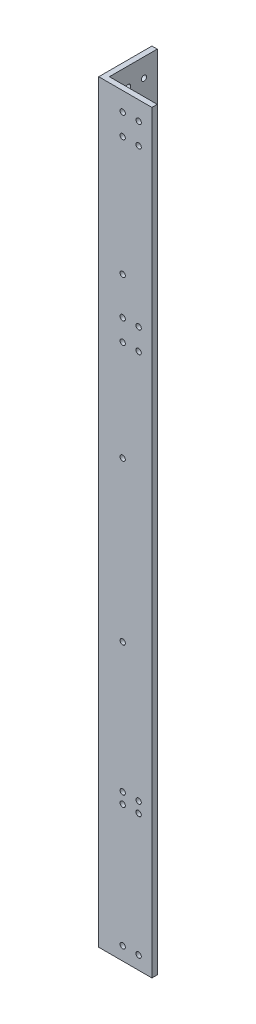
SolidWorks part; units mm, degrees
ref_plane "Front Plane" through (0, 0, 0) normal (0, 0, 1) x (1, 0, 0)
ref_plane "Top Plane" through (0, 0, 0) normal (0, 1, 0) x (1, 0, 0)
ref_plane "Right Plane" through (0, 0, 0) normal (1, 0, 0) x (0, 0, -1)
sketch "Sketch2" plane through (0, 0, 0) normal (0, 1, 0) x (1, 0, 0)
  line L0 (0, 31.75) -> (3.175, 31.75)
  line L1 (3.175, 31.75) -> (3.175, 3.175)
  line L2 (3.175, 3.175) -> (31.75, 3.175)
  line L3 (31.75, 3.175) -> (31.75, 0)
  line L4 (31.75, 0) -> (0, 0)
  line L5 (0, 0) -> (0, 31.75)
  point P9 (1.5875, 31.75)
  point P10 (31.75, 1.5875)
  dimension "D4" = 3.175
  dimension "D1" = 31.75
  dimension "D2" = 31.75
  dimension "D3" = 3.175
extrude "Boss-Extrude1" add sketch "Sketch2" along normal blind 450
sketch "LeftSideHoles-Sketch3" plane through (0, 0, 0) normal (0, 0, 1) x (1, 0, 0)
  line L0 (0, 0) -> (31.75, 0) construction
  line L3 (0, 450) -> (0, 0) construction
  circle A0 centre (14.2875, 81.1125) radius 1.5875
  circle A1 centre (23.8125, 81.1125) radius 1.5875
  circle A2 centre (14.2875, 87.4625) radius 1.5875
  circle A3 centre (23.8125, 87.4625) radius 1.5875
  circle A4 centre (14.2875, 438.8875) radius 1.5875
  circle A5 centre (14.2875, 426.1875) radius 1.5875
  circle A6 centre (23.8125, 438.8875) radius 1.5875
  circle A7 centre (23.8125, 426.1875) radius 1.5875
  circle A10 centre (14.2875, 332.6026) radius 1.5875
  circle A11 centre (23.8125, 332.6026) radius 1.5875
  circle A12 centre (14.2875, 319.9026) radius 1.5875
  circle A13 centre (23.8125, 319.9026) radius 1.5875
  circle A14 centre (14.2875, 7.9375) radius 1.5875
  circle A15 centre (23.8125, 7.9375) radius 1.5875
  circle A16 centre (14.2875, 165) radius 1.5875
  circle A17 centre (14.2875, 260) radius 1.5875
  circle A18 centre (14.2875, 355) radius 1.5875
  point P24 (15.875, 0)
  dimension "D4" = 3.175
  dimension "D1" = 81.1125
  dimension "D2" = 14.2875
  dimension "D8" = 11.1125
  dimension "D10" = 7.9375
  dimension "D5" = 6.35
  dimension "D7" = 12.7
  dimension "D9" = 12.7
  dimension "D3" = 9.525
  dimension "D11" = 332.6026
  dimension "D12" = 165
  dimension "D13" = 95
  dimension "D14" = 95
sketch "BackSideHoles-Sketch4" plane through (0, 0, 0) normal (-1, 0, 0) x (0, 0, 1)
  line L0 (-31.75, 450) -> (0, 450) construction
  line L1 (0, 450) -> (0, 0) construction
  line L3 (-31.75, 0) -> (0, 0) construction
  circle A0 centre (-23.8125, 81.1125) radius 1.5875
  circle A1 centre (-14.2875, 81.1125) radius 1.5875
  circle A2 centre (-23.8125, 87.4625) radius 1.5875
  circle A3 centre (-14.2875, 87.4625) radius 1.5875
  circle A4 centre (-23.8125, 438.8875) radius 1.5875
  circle A5 centre (-14.2875, 438.8875) radius 1.5875
  circle A6 centre (-23.8125, 426.1875) radius 1.5875
  circle A7 centre (-14.2875, 426.1875) radius 1.5875
  circle A10 centre (-23.8125, 332.6026) radius 1.5875
  circle A11 centre (-14.2875, 332.6026) radius 1.5875
  circle A12 centre (-23.8125, 326.2526) radius 1.5875
  circle A13 centre (-14.2875, 326.2526) radius 1.5875
  circle A14 centre (-14.2875, 165) radius 1.5875
  circle A15 centre (-14.2875, 260) radius 1.5875
  circle A16 centre (-14.2875, 355) radius 1.5875
  circle A17 centre (-23.8125, 7.9375) radius 1.5875
  circle A18 centre (-14.2875, 7.9375) radius 1.5875
  dimension "D4" = 3.175
  dimension "D2" = 14.2875
  dimension "D5" = 6.35
  dimension "D7" = 12.7
  dimension "D3" = 81.1125
  dimension "D6" = 11.1125
  dimension "D8" = 6.35
  dimension "D9" = 9.525
  dimension "D1" = 332.6026
  dimension "D10" = 165
  dimension "D11" = 95
  dimension "D12" = 95
  dimension "D13" = 7.9375
extrude "LeftSideHoles-Cut-Extrude1" cut sketch "LeftSideHoles-Sketch3" against normal blind 3.175
extrude "BackSideHoles-Cut-Extrude2" cut sketch "BackSideHoles-Sketch4" against normal blind 3.175
equation "\"RailThickness\"= .125in'Spec"
equation "\"VSWidth\"= 1.25in'Spec"
equation "\"VSHeight\"= 1.25in'Spec"
equation "\"VSLength\"= 450mm"
equation "\"HoleOffsetFromEdge\"= \"RailThickness\" * 2.5"
equation "\"HoleOffsetFromSide\"= \"RailThickness\" * 3.5"
equation "\"LegHeight\"= 70mm'Space needed for PSU/Stepper/Electronics"
equation "\"VSBottomSideRailHoleY1FromBottomOfLowerRail\"= \"V1 BottomOfLowerRail\" + \"HoleOffsetFromSide\"'Equals 70.1125"
equation "\"VSSideRailHoleX1FromSide\"= \"HoleOffsetFromSide\" + \"RailThickness\""
equation "\"FasteningHoleDiameter\"= .125in"
equation "\"VSBottomSideRailHoleY2FromY1\"= \"LowerRailHeight\" - \"HoleOffsetFromSide\" - \"HoleOffsetFromEdge\"'Equals 6.35"
equation "\"VSTopSideRailHoleY1FromEdge\"= \"HoleOffsetFromEdge\" + \"RailThickness\""
equation "\"D4@LeftSideHoles-Sketch3\"=\"FasteningHoleDiameter\""
equation "\"D1@LeftSideHoles-Sketch3\"=\"VSBottomSideRailHoleY1FromBottomOfLowerRail\""
equation "\"D2@LeftSideHoles-Sketch3\"=\"VSSideRailHoleX1FromSide\""
equation "\"D1@Boss-Extrude1\"=\"VSLength\""
equation "\"D4@BackSideHoles-Sketch4\" = \"FasteningHoleDiameter\""
equation "\"D3@BackSideHoles-Sketch4\"=\"VSBottomSideRailHoleY1FromBottomOfLowerRail\""
equation "\"D2@BackSideHoles-Sketch4\" = \"VSSideRailHoleX1FromSide\""
equation "\"D8@LeftSideHoles-Sketch3\"=\"VSTopSideRailHoleY1FromEdge\""
equation "\"VSMidSideRailHoleY1FromV8TopOfMidSideRail\"= \"V8 ToTopOfMidSideRail\" - \"HoleOffsetFromEdge\"'Equals 308.2875"
equation "\"LowerRailHeight\"= 1.00in"
equation "\"D1@Sketch2\"=\"VSHeight\""
equation "\"D2@Sketch2\"=\"VSWidth\""
equation "\"MidBackRailHeight\"= 1.00in"
equation "\"VSMidBackRailHoleY1FromV7TopOfMidBackRail\"= \"V7 ToTopOfMidBackRail\" - \"HoleOffsetFromSide\"'Equals 308.2875"
equation "\"TopRailHeight\"= 1.25in"
equation "\"MidSideRailHeight\"= 1.25in"
equation "\"D10@LeftSideHoles-Sketch3\"=\"HoleOffsetFromEdge\""
equation "\"D5@LeftSideHoles-Sketch3\"=\"VSBottomSideRailHoleY2FromY1\""
equation "\"D5@BackSideHoles-Sketch4\"=\"VSBottomSideRailHoleY2FromY1\""
equation "\"VSMidBackRailHoleY2FromY1\"= \"MidBackRailHeight\" - \"HoleOffsetFromSide\" - \"HoleOffsetFromEdge\"'Equals 6.35"
equation "\"VSMidSideRailHoleY2FromY1\"= \"MidSideRailHeight\" - \"HoleOffsetFromSide\" - \"HoleOffsetFromEdge\"'Equals 12.7"
equation "\"D7@LeftSideHoles-Sketch3\"=\"VSMidSideRailHoleY2FromY1\""
equation "\"D8@BackSideHoles-Sketch4\"=\"VSMidBackRailHoleY2FromY1\""
equation "\"D6@BackSideHoles-Sketch4\"=\"VSTopSideRailHoleY1FromEdge\""
equation "\"VSTopSideRailHoleY2FromY1\"= \"TopRailHeight\" - \"VSTopSideRailHoleY1FromEdge\" - \"HoleOffsetFromEdge\"'Equals 12.7"
equation "\"D7@BackSideHoles-Sketch4\"=\"VSTopSideRailHoleY2FromY1\""
equation "\"D9@LeftSideHoles-Sketch3\"=\"VSTopSideRailHoleY2FromY1\""
equation "\"VSBottomSideRailHoleX2FromX1\"= \"VSWidth\" - \"VSSideRailHoleX1FromSide\" - \"HoleOffsetFromEdge\""
equation "\"D3@LeftSideHoles-Sketch3\"=\"VSBottomSideRailHoleX2FromX1\""
equation "\"D9@BackSideHoles-Sketch4\"=\"VSBottomSideRailHoleX2FromX1\""
equation "\"V1 BottomOfLowerRail\"= \"LegHeight\""
equation "\"StepperShaftLength\"= 24mm'Pulley will be attached to the end"
equation "\"ZAxisLeadScrewLength\"= 200mm"
equation "\"LM8UUHeight\"= 24mm'Spec"
equation "\"V2 ToBedAtTopOfZAxis\"= \"V1 BottomOfLowerRail\" + \"StepperShaftLength\" + \"ZAxisLeadScrewLength\" - \"LM8UUHeight\" / 2"
equation "\"HotEndToTopOfXAxisGB\"= 63.315144mm'Measured from the100.Should be 63.315144"
equation "\"TopOfGBToBottomOfLinearRail\"= \"LinearGBWidth\" / 2 + \"LinearRailWidth\" / 2"
equation "\"LinearGBWidth\"= 27mm'Spec"
equation "\"V5 ToBottomOfXAxisLinearRail\"= \"V4 ToTopOfBuildPlate/HotEndTip\" + \"HotEndToTopOfXAxisGB\" - \"TopOfGBToBottomOfLinearRail\""
equation "\"LinearRailWidth\"= 12mm'Spec"
equation "\"V6 ToBottomOfGantryPulley\"= \"V5 ToBottomOfXAxisLinearRail\" - \"DistanceFromGABTopToLowerPulley\""
equation "\"GABUpperHeight\"= 6mm"
equation "\"GABMidWallHeight\"= 28mm'Must equal 28 or changes alignment"
equation "\"20TGT2PulleyWidth\"= 8.7mm'The STL of the Pulley in the diagram is a bit larger"
equation "\"GABMidShortRiserHeight\"= \"GABMidWallHeight\" / 2 - \"20TGT2PulleyWidth\"'Equals 5.3"
equation "\"GABRiserBossOffset\"= 0.8mm'Aligns Pulleys"
equation "\"DistanceFromGABTopToLowerPulley\"= \"GABUpperHeight\" + \"GABMidWallHeight\" - \"GABMidShortRiserHeight\" + \"GABRiserBossOffset\" / 2"
equation "\"V7 ToTopOfMidBackRail\"= \"V6 ToBottomOfGantryPulley\" + \"StepperShaftLength\""
equation "\"D1@BackSideHoles-Sketch4\" = \"VSMidBackRailHoleY1FromV7TopOfMidBackRail\""
equation "\"D11@LeftSideHoles-Sketch3\"=\"VSMidSideRailHoleY1FromV8TopOfMidSideRail\""
equation "\"V4 ToTopOfBuildPlate/HotEndTip\"= \"V2 ToBedAtTopOfZAxis\" + \"BedToBuildPlateStandoffLength\" + \"BuildPlateHeight\""
equation "\"BedToBuildPlateStandoffLength\"= 15mm"
equation "\"BuildPlateHeight\"= 8mm'Spec"
equation "\"V8 ToTopOfMidSideRail\"= \"V7 ToTopOfMidBackRail\" - \"RailThickness\""
equation "\"VSEnclosureOffsets\"= ( \"VSLength\" - \"LegHeight\" ) / 4"
equation "\"D12@LeftSideHoles-Sketch3\"=\"LegHeight\" + \"VSEnclosureOffsets\""
equation "\"D13@LeftSideHoles-Sketch3\"=\"VSEnclosureOffsets\""
equation "\"D14@LeftSideHoles-Sketch3\"=\"VSEnclosureOffsets\""
equation "\"D10@BackSideHoles-Sketch4\"=\"LegHeight\" + \"VSEnclosureOffsets\""
equation "\"D11@BackSideHoles-Sketch4\"=\"VSEnclosureOffsets\""
equation "\"D12@BackSideHoles-Sketch4\"=\"VSEnclosureOffsets\""
equation "\"D13@BackSideHoles-Sketch4\"=\"HoleOffsetFromEdge\""
